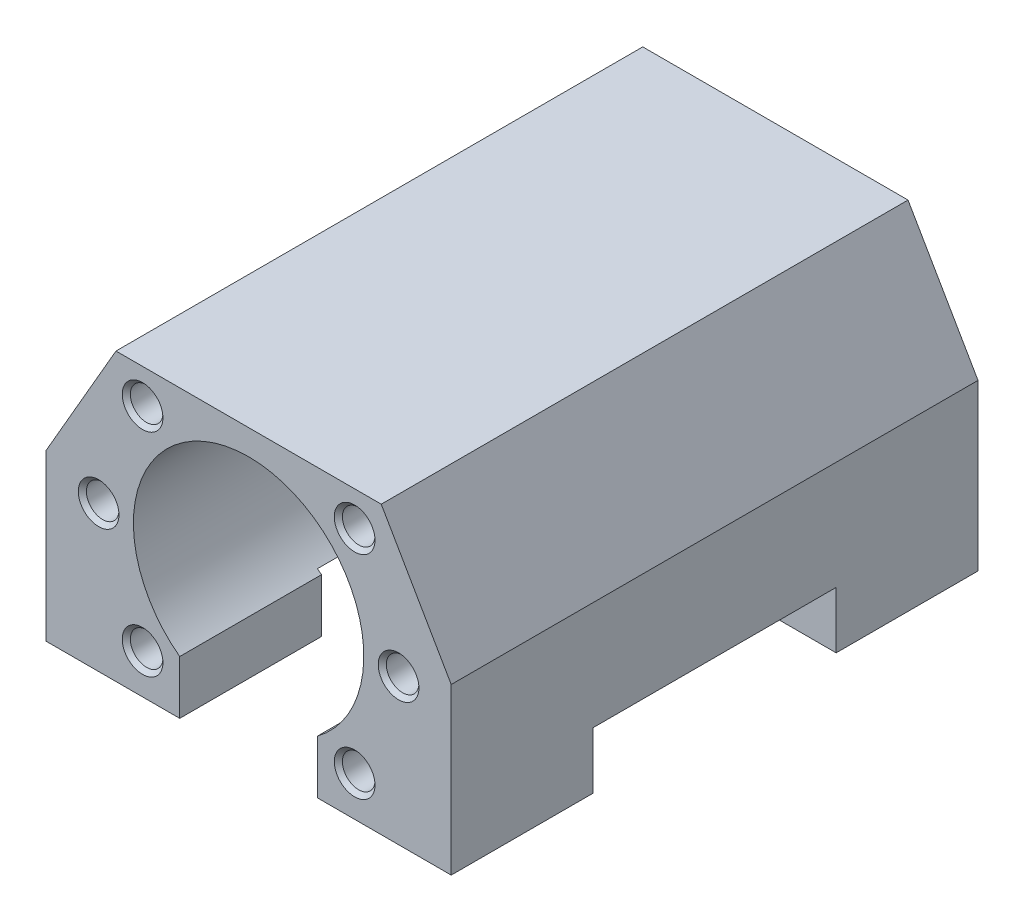
SolidWorks part; units mm, degrees
material "7050-T7651"
ref_plane "Front Plane" through (0, 0, 0) normal (0, 0, 1) x (1, 0, 0)
ref_plane "Top Plane" through (0, 0, 0) normal (0, 1, 0) x (1, 0, 0)
ref_plane "Right Plane" through (0, 0, 0) normal (1, 0, 0) x (0, 0, -1)
sketch "Sketch1" plane through (0, 0, 0) normal (0, 0, 1) x (1, 0, 0)
  line L0 (0, 22) -> (-20.7846, 22) construction
  line L1 (-20.7846, 22) -> (20.7846, 22)
  line L2 (-31.75, 3.0074) -> (-31.75, -22.86)
  line L3 (-31.75, -22.86) -> (31.75, -22.86)
  line L4 (31.75, 3.0074) -> (31.75, -22.86)
  line L5 (-23.6537, 17.0306) -> (31.75, -22.86) construction
  line L6 (-31.75, -22.86) -> (23.6537, 17.0306) construction
  line L7 (-20.7846, 22) -> (-31.75, 3.0074)
  line L9 (0, 22) -> (0, -22.86) construction
  line L10 (20.7846, 22) -> (31.75, 3.0074)
  circle A0 centre (0, 0) radius 29 construction
  circle A1 centre (0, 0) radius 18.05
  dimension "D1" = 22
  dimension "D3" = 36.1
  dimension "D4" = 22.86
  dimension "D2" = 58
  dimension "D5" = 30
  dimension "D6" = 63.5
extrude "Boss-Extrude1" add sketch "Sketch1" along normal mid plane 82.55
sketch "Sketch6" plane through (0, -22.86, 0) normal (0, -1, 0) x (1, 0, 0)
  line L0 (-31.75, 41.275) -> (-31.75, -41.275) construction
  line L4 (-31.75, 19.05) -> (31.75, 19.05)
  line L5 (-31.75, 19.05) -> (-31.75, -19.05)
  line L6 (-31.75, -19.05) -> (31.75, -19.05)
  line L7 (31.75, 19.05) -> (31.75, -19.05)
  line L8 (-31.75, 19.05) -> (31.75, -19.05) construction
  line L9 (-31.75, -19.05) -> (31.75, 19.05) construction
  point P7 (0, 0)
  dimension "D1" = 38.1
extrude "Cut-Extrude1" cut sketch "Sketch6" against normal blind 8.89
sketch "Sketch12" plane through (0, -13.97, 0) normal (0, -1, 0) x (1, 0, 0)
  line L2 (-22, 6.35) -> (22, 6.35)
  line L3 (-22, 6.35) -> (-22, -6.35)
  line L4 (-22, -6.35) -> (22, -6.35)
  line L5 (22, 6.35) -> (22, -6.35)
  line L6 (-22, 6.35) -> (22, -6.35) construction
  line L7 (-22, -6.35) -> (22, 6.35) construction
  point P4 (0, 0)
  dimension "D1" = 12.7
  dimension "D2" = 44
extrude "Boss-Extrude2" add sketch "Sketch12" against normal up to next
sketch "Sketch7" plane through (0, -22.86, 0) normal (0, -1, 0) x (1, 0, 0)
  line L0 (-31.75, 41.275) -> (31.75, 41.275) construction
  line L3 (-10.795, 41.275) -> (10.795, 41.275)
  line L4 (-10.795, 41.275) -> (-10.795, -41.275)
  line L5 (-10.795, -41.275) -> (10.795, -41.275)
  line L6 (10.795, 41.275) -> (10.795, -41.275)
  line L7 (-10.795, 41.275) -> (10.795, -41.275) construction
  line L8 (-10.795, -41.275) -> (10.795, 41.275) construction
  point P5 (0, 0)
  dimension "D1" = 21.59
extrude "Cut-Extrude2" cut sketch "Sketch7" against normal blind 35
fillet "Fillet1" radius 10.795 2 edges at (10.795, 12.14, 0) (-10.795, 12.14, 0)
hole_wizard "1/4-20 Tapped Hole1" positions "Sketch4" profile "Sketch3" tap size "1/4-20" standard "ANSI Inch"
sketch "Sketch4" plane through (0, 0, 41.275) normal (0, 0, 1) x (1, 0, 0)
  line L1 (16.617, -16.617) -> (-16.617, 16.617) construction
  line L3 (-16.617, -16.617) -> (16.617, 16.617) construction
  line L5 (0, 0) -> (23.5, 0) construction
  circle A0 centre (0, 0) radius 23.5 construction
  point P1 (-16.617, 16.617)
  point P4 (-23.5, 0)
  point P7 (-16.617, -16.617)
  point P10 (16.617, -16.617)
  point P13 (23.5, 0)
  point P16 (16.617, 16.617)
  dimension "D1" = 47
  dimension "D2" = 45
  dimension "D3" = 45
sketch "Sketch3" plane through (-16.617, 16.617, 41.275) normal (1, 0, 0) x (0, -1, 0)
  line L0 (0, 0) -> (0, 18.0438)
  line L1 (0, 18.0438) -> (2.5527, 16.51)
  line L2 (2.5527, 16.51) -> (2.5527, 0.635)
  line L3 (2.5527, 0.635) -> (3.1877, 0)
  line L5 (3.1877, 0) -> (0, 0)
  line L6 (-2.5527, 0.635) -> (-3.1877, 0) construction
  line L10 (0, 18.0438) -> (-2.5527, 16.51) construction
  line L11 (0, -6.35) -> (0, 107.95) construction
  dimension "Tap Drill Dia." = 5.1054
  dimension "Tap Drill Depth" = 16.51
  dimension "Near C'Sink Dia." = 6.3754
  dimension "Near C'Sink Angle" = 90
  dimension "Drill Angle" = 118
cosmetic thread "Hole Thread1" parameters "D1"=12.7, "D2"=6.35
cosmetic thread "Hole Thread2" parameters "D1"=12.7, "D2"=6.35
cosmetic thread "Hole Thread3" parameters "D1"=12.7, "D2"=6.35
cosmetic thread "Hole Thread4" parameters "D1"=12.7, "D2"=6.35
cosmetic thread "Hole Thread5" parameters "D1"=12.7, "D2"=6.35
cosmetic thread "Hole Thread6" parameters "D1"=12.7, "D2"=6.35
mirror "Mirror1" about plane through (0, 0, 0) normal (0, 0, 1) of "1/4-20 Tapped Hole1"
hole_wizard "5/16-18 Tapped Hole1" positions "Sketch13" profile "Sketch14" tap size "5/16-18" standard "ANSI Inch"
sketch "Sketch13" plane through (0, -13.97, 0) normal (0, -1, 0) x (-1, 0, 0)
  line L0 (-25.4, 0) -> (25.4, 0) construction
  point P0 (-25.4, 0)
  point P2 (25.4, 0)
  point P8 (0, 0)
  dimension "D1" = 50.8
cosmetic thread "Hole Thread11" parameters "D1"=16.002, "D2"=7.9375
cosmetic thread "Hole Thread12" parameters "D1"=16.002, "D2"=7.9375
sketch "Sketch14" plane through (25.4, -13.97, 0) normal (1, 0, 0) x (0, 0, -1)
  line L0 (0, 0) -> (0, 22.2811)
  line L1 (0, 22.2811) -> (3.2639, 20.32)
  line L2 (3.2639, 20.32) -> (3.2639, 1.3398)
  line L3 (3.2639, 1.3398) -> (4.6037, 0)
  line L5 (4.6037, 0) -> (0, 0)
  line L6 (-3.2639, 1.3398) -> (-4.6037, 0) construction
  line L10 (0, 22.2811) -> (-3.2639, 20.32) construction
  line L11 (0, -6.35) -> (0, 107.95) construction
  dimension "Tap Drill Dia." = 6.5278
  dimension "Tap Drill Depth" = 20.32
  dimension "Near C'Sink Dia." = 9.2075
  dimension "Near C'Sink Angle" = 90
  dimension "Drill Angle" = 118
